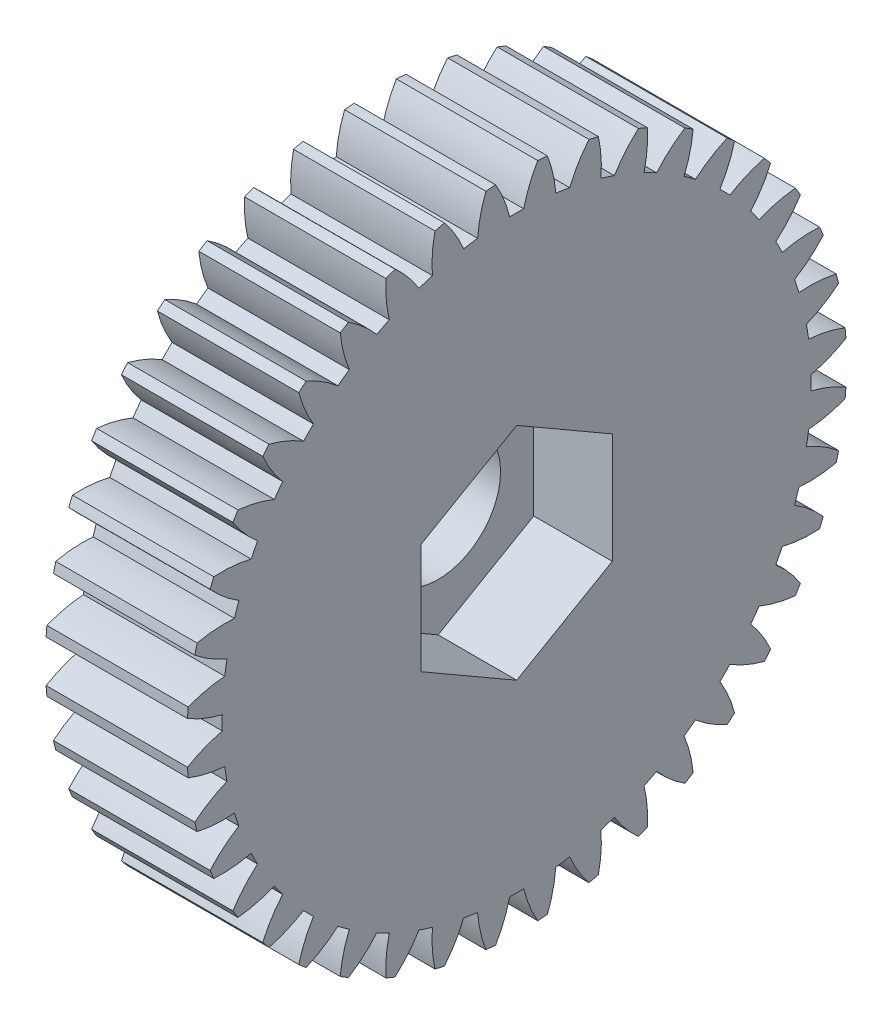
SolidWorks part; units mm, degrees
ref_plane "Plane1" through (0, 0, 0) normal (0, 0, 1) x (1, 0, 0)
ref_plane "Plane2" through (0, 0, 0) normal (0, 1, 0) x (1, 0, 0)
ref_plane "Plane3" through (0, 0, 0) normal (1, 0, 0) x (0, 0, -1)
sketch "HoldingSke" plane through (0, 0, 0) normal (0, 1, 0) x (1, 0, 0)
  line L0 (0, 0) -> (0.766, -0.6428)
  line L1 (-15, 0) -> (100, 0) construction
  line L2 (0, 0) -> (-2.1039, 2.3779)
  line L3 (0, 0) -> (-11.863, 4.5341)
  line L4 (0, 0) -> (6.6156, 5.5511)
  line L5 (0, 0) -> (-46.8476, -17.4728)
  line L6 (0, 0) -> (-7.4607, -5.0337)
  line L7 (-2.1039, 2.3779) -> (8.6586, 51.2059)
  line L8 (-76.2, 54.61) -> (-75.5, 54.61)
  line L9 (-71.009, 38.7566) -> (-53.1078, 45.2721)
  line L10 (-76.2, 71.12) -> (104.1128, 71.12)
  line L11 (0, 0) -> (-9, 0)
  line L12 (-76.2, 101.6) -> (-76.162, 101.6)
  line L13 (24.9733, 27.94) -> (52.9518, 28.4284)
  line L14 (24.9733, 27.94) -> (24.9743, 27.94)
  line L15 (24.9733, 27.94) -> (100.4006, 29.5858)
  line L16 (-63.627, -1) -> (-12.827, -1)
  circle A0 centre (0, 0) radius 2
  circle A1 centre (0, 0) radius 18.749
  circle A2 centre (0, 0) radius 37.5
  circle A3 centre (0, 0) radius 2
  dimension "MHD" = 37.498
  dimension "Hub_dia" = 75
  dimension "Bore" = 4
  dimension "MBD" = 4
  dimension "Num_teeth" = 40
  dimension "Pitch" = 1
  dimension "Overall_len" = 50
  dimension "Show_teeth" = 40
  dimension "Thickness" = 9
  dimension "OAL" = 50.0001
  dimension "T_dim" = 0.7
  dimension "Ap" = 20
  dimension "H" = 19.05
  dimension "Pitch_radius" = 180.3128
  dimension "Width" = 9
  dimension "Backlash" = 0.038
  dimension "Addendum_fac" = 1
  dimension "Dedendum_fac" = 1.25
  dimension "Clearance_fac" = 0.25
  dimension "Dedendum_add" = 0.001
  dimension "Module" = 1
sketch "BasProSke" plane through (0, 0, 0) normal (0, 1, 0) x (1, 0, 0)
  line L0 (-10, 0) -> (60, 0) construction
  line L1 (0, 0) -> (0, 21)
  line L2 (0, 0) -> (9, 0)
  line L3 (9, 0) -> (9, 21)
  line L4 (9, 21) -> (0, 21)
  dimension "Thickness" = 9
  dimension "Diameter" = 42
revolve "Base-Revolve" add sketch "BasProSke" angle 360 about L0
sketch "TooCutSke" plane through (0, 0, 0) normal (1, 0, 0) x (0, 0, -1)
  line L1 (0, 0) -> (0, 107) construction
  line L2 (0, 0) -> (-0.8517, 19.9819) construction
  line L3 (0, 0) -> (-3.1363, 39.8509) construction
  line L4 (-0.8517, 19.9819) -> (-1.5682, 19.9255) construction
  arc A0 (0.4487, 18.7436) -> (-0.4487, 18.7436) centre (0, 0) ccw
  arc A1 (1.3547, 20.9817) -> (-1.3547, 20.9817) centre (0, 0) ccw
  circle A2 centre (0, 0) radius 20 construction
  circle A3 centre (0, 0) radius 18.7939 construction
  arc A4 (-0.4487, 18.7436) -> (-1.3547, 20.9817) centre (-8.2322, 16.895) ccw
  arc A5 (1.3547, 20.9817) -> (0.4487, 18.7436) centre (8.2322, 16.895) ccw
  dimension "Root_dia" = 37.498
  dimension "Overcut_dia" = 42.0508
  dimension "Pitch_dia" = 40
  dimension "Base_dia" = 37.5877
  dimension "Flank_rad" = 8
  dimension "Half_ang" = 4.5
  dimension "Half_CT" = 0.7187
extrude "ToothCut" cut sketch "TooCutSke" along normal through all
fillet "Breaks" [suppressed] radius 0.02 tangent propagation no
fillet "RootFillets" [suppressed] radius 0.251
pattern_circular "TeethCuts" count 40 every 9 about axis through (-10, 0, 0) along (1, 0, 0) of "ToothCut", "RootFillets", "Breaks"
sketch "HubNeaOneSke" plane through (0, 0, 0) normal (-1, 0, 0) x (0, 0, 1)
  circle A0 centre (0, 0) radius 18.749
  dimension "Diameter" = 37.498
extrude "HubNearOne" [suppressed] add sketch "HubNeaOneSke" along normal blind 41.0001
sketch "HubNeaBotSke" plane through (0, 0, 0) normal (-1, 0, 0) x (0, 0, 1)
  circle A0 centre (0, 0) radius 18.749
  dimension "Diameter" = 37.498
extrude "HubNearBoth" [suppressed] add sketch "HubNeaBotSke" along normal blind 20.5
ref_plane "FarPln" through (9, 0, 0) normal (1, 0, 0) x (0, 0, -1)
sketch "HubFarSke" plane through (9, 0, 0) normal (1, 0, 0) x (0, 0, -1)
  circle A0 centre (0, 0) radius 18.749
  dimension "Diameter" = 37.498
extrude "HubFar" [suppressed] add sketch "HubFarSke" along normal blind 20.5
sketch "BorSke" plane through (0, 0, 0) normal (1, 0, 0) x (0, 0, -1)
  circle A0 centre (0, 0) radius 2
  dimension "Diameter" = 4
extrude "Bore" cut sketch "BorSke" along normal mid plane 100.0001
sketch "KeySke" plane through (0, 0, 0) normal (1, 0, 0) x (0, 0, -1)
  line L0 (-0.8, 0) -> (-0.8, 2.7)
  line L1 (-0.8, 2.7) -> (0.8, 2.7)
  line L2 (0.8, 2.7) -> (0.8, 0)
  line L3 (0, 0) -> (0, 34) construction
  line L4 (-0.8, 0) -> (0.8, 0)
  dimension "Offset" = 2.7
  dimension "Width" = 1.6
extrude "Keyway" [suppressed] cut sketch "KeySke" along normal mid plane 100.0001
pattern_circular "Keyway2" [suppressed] count 2 every 90 about axis through (-10, 0, 0) along (1, 0, 0) reverse direction yes
sketch "Sketch1" plane through (9, 0, 0) normal (1, 0, 0) x (0, 0, -1)
  line L1 (0, 7.025) -> (-6.0838, 3.5125)
  line L2 (-6.0838, 3.5125) -> (-6.0838, -3.5125)
  line L3 (-6.0838, -3.5125) -> (0, -7.025)
  line L4 (0, -7.025) -> (6.0838, -3.5125)
  line L5 (6.0838, -3.5125) -> (6.0838, 3.5125)
  line L6 (6.0838, 3.5125) -> (0, 7.025)
  circle A0 centre (0, 0) radius 7.025
  circle A2 centre (0, 0) radius 6.0838 construction
  circle A3 centre (0, 0) radius 3.9725
  dimension "D1" = 7.945
  dimension "D3" = 14.05
extrude "Cut-Extrude1" cut sketch "Sketch1" against normal blind 5 contours L1 L2 L3 L4 L5 L6
extrude "Cut-Extrude2" cut sketch "Sketch1<7>" against normal through all contours A3 region at (9, 0, 0)
sketch "Sketch1<7>" plane through (9, 0, 0) normal (1, 0, 0) x (0, 0, -1) same geometry as "Sketch1"
sketch "Sketch2" plane through (0, 0, 0) normal (-1, 0, 0) x (0, 0, 1)
  circle A0 centre (0, 0) radius 6
  circle A1 centre (0, 0) radius 4
  dimension "D1" = 12
  dimension "D2" = 8
extrude "Boss-Extrude1" add sketch "Sketch2" along normal blind 1.3
equation "' \"Module@HoldingSke\" = 6.35"
equation "' \"Num_teeth@HoldingSke\" = 12"
equation "' \"Ap@HoldingSke\" =  20"
equation "' \"Ap@HoldingSke\" = 20"
equation "' \"Width@HoldingSke\" = 0.5 * 25.4"
equation "' \"Hub_dia@HoldingSke\"= 1 * 25.4"
equation "' \"Hub_dia@HoldingSke\" = 1 * 25.4"
equation "' \"Overall_len@HoldingSke\" = 1.0 * 25.4"
equation "' \"Bore@HoldingSke\" = 0.75 * 25.4"
equation "' \"T_dim@HoldingSke\" = 0.1 * 25.4"
equation "' \"Width@KeySke\" = 0.25 * 25.4"
equation "' \"Show_teeth@HoldingSke\" = 13"
equation "' \"Backlash@HoldingSke\" = 0.009 * 25.4"
equation "' \"Addendum_fac@HoldingSke\" = 1.0"
equation "' \"Dedendum_fac@HoldingSke\" = 1.25"
equation "' \"Dedendum_add@HoldingSke\" = 0.00005 * 25.4"
equation "' \"Clearance_fac@HoldingSke\" = 0.25"
equation "\"Pitch@HoldingSke\" = 1 / \"Module@HoldingSke\""
equation "\"Overcut_dia@TooCutSke\" = (\"Num_teeth@HoldingSke\" + 2 * \"Addendum_fac@HoldingSke\") / \"Pitch@HoldingSke\" + 0.002 * 25.4"
equation "\"Pitch_dia@TooCutSke\" = \"Num_teeth@HoldingSke\" / \"Pitch@HoldingSke\""
equation "\"Base_dia@TooCutSke\" = \"Num_teeth@HoldingSke\" / \"Pitch@HoldingSke\" * cos((\"Ap@HoldingSke\"  * 3.14159265 / 180))"
equation "\"Root_dia@TooCutSke\" = (\"Num_teeth@HoldingSke\" + 2) / \"Pitch@HoldingSke\" - 2 * (\"Addendum_fac@HoldingSke\" + \"Dedendum_fac@HoldingSke\") / \"Pitch@HoldingSke\" - \"Dedendum_add@HoldingSke\" * 2"
equation "\"Half_ang@TooCutSke\" = 180 / \"Num_teeth@HoldingSke\""
equation "\"Half_CT@TooCutSke\" = \"Num_teeth@HoldingSke\" / \"Pitch@HoldingSke\" * sin((3.14159265 / 2 / \"Num_teeth@HoldingSke\")) / 2 - 7 * \"Backlash@HoldingSke\" / 4"
equation "\"Flank_rad@TooCutSke\" = \"Num_teeth@HoldingSke\" / \"Pitch@HoldingSke\" / 5"
equation "\"Radius@RootFillets\" = \"Clearance_fac@HoldingSke\" / \"Pitch@HoldingSke\" + \"Dedendum_add@HoldingSke\""
equation "\"Break_rad@Breaks\" = 0.02 / \"Pitch@HoldingSke\""
equation "\"Thickness@HoldingSke\" = \"Width@HoldingSke\""
equation "\"OAL@HoldingSke\" = \"Thickness@HoldingSke\""
equation "\"MHD@HoldingSke\" = (\"Num_teeth@HoldingSke\" + 2) / \"Pitch@HoldingSke\" - 2 * (\"Addendum_fac@HoldingSke\" + \"Dedendum_fac@HoldingSke\")  / \"Pitch@HoldingSke\" - \"Dedendum_add@HoldingSke\" * 2"
equation "\"MBD@HoldingSke\" = (\"Num_teeth@HoldingSke\" + 2) / \"Pitch@HoldingSke\" - 2 * (\"Addendum_fac@HoldingSke\" + \"Dedendum_fac@HoldingSke\")  / \"Pitch@HoldingSke\" - \"Dedendum_add@HoldingSke\" * 2 - 0.002 * 25.4"
equation "\"MHD@HoldingSke\" = ((sgn( \"MHD@HoldingSke\" - \"Hub_dia@HoldingSke\" )-1)*( \"MHD@HoldingSke\" - \"Hub_dia@HoldingSke\" ))/-2+ \"Hub_dia@HoldingSke\""
equation "\"MBD@HoldingSke\" = ((sgn( \"MBD@HoldingSke\" - \"Bore@HoldingSke\" )-1)*( \"MBD@HoldingSke\" - \"Bore@HoldingSke\" ))/-2+ \"Bore@HoldingSke\""
equation "\"OAL@HoldingSke\" = ((sgn( \"OAL@HoldingSke\" - \"Overall_len@HoldingSke\" )+1)*( \"OAL@HoldingSke\" - \"Overall_len@HoldingSke\" ))/2 + \"Overall_len@HoldingSke\" + 0.000002 * 25.4"
equation "\"Num_teeth@TeethCuts\" = int( \"Show_teeth@HoldingSke\" ) + 1"
equation "\"Num_teeth@TeethCuts\" = ((sgn( \"Num_teeth@TeethCuts\" - \"Num_teeth@HoldingSke\" )-1)*( \"Num_teeth@TeethCuts\" - \"Num_teeth@HoldingSke\" ))/-2+ \"Num_teeth@HoldingSke\""
equation "\"Num_teeth@TeethCuts\" = ((sgn( \"Num_teeth@TeethCuts\" - 2.0)+1)*( \"Num_teeth@TeethCuts\" - 2.0))/2 +2.0"
equation "\"Angle@TeethCuts\" = 360.0 / \"Num_teeth@HoldingSke\""
equation "\"Diameter@BasProSke\" = (\"Num_teeth@HoldingSke\" + 2 * \"Addendum_fac@HoldingSke\") / \"Pitch@HoldingSke\""
equation "\"Thickness@BasProSke\"  = \"Thickness@HoldingSke\""
equation "' \"Fillet_rad@BasProSke\" =  \"Thickness@HoldingSke\" * 0.05"
equation "' \"Fillet_rad@BasProSke\" = \"Thickness@HoldingSke\" * 0.05"
equation "\"MHD@HoldingSke\" = ((sgn( \"MHD@HoldingSke\" - \"Root_dia@TooCutSke\" )-1)*( \"MHD@HoldingSke\" - \"Root_dia@TooCutSke\" ))/-2+ \"Root_dia@TooCutSke\""
equation "\"Diameter@HubNeaOneSke\" = \"MHD@HoldingSke\""
equation "\"Length@HubNearOne\" = \"OAL@HoldingSke\" - \"Thickness@BasProSke\""
equation "\"Diameter@HubNeaBotSke\" = \"MHD@HoldingSke\""
equation "\"Length@HubNearBoth\" = ( \"OAL@HoldingSke\" - \"Thickness@BasProSke\" ) / 2.0"
equation "\"Thickness@FarPln\" = \"Thickness@BasProSke\""
equation "\"Diameter@HubFarSke\" = \"MHD@HoldingSke\""
equation "\"Length@HubFar\" = ( \"OAL@HoldingSke\" - \"Thickness@BasProSke\" ) / 2.0"
equation "\"Diameter@BorSke\" = \"MBD@HoldingSke\""
equation "\"D1@Bore\" = \"OAL@HoldingSke\" * 2.0"
equation "\"D1@Keyway\" = \"OAL@HoldingSke\" * 2.0"
equation "\"Offset@KeySke\" = \"T_dim@HoldingSke\" + \"MBD@HoldingSke\" / 2.0"
